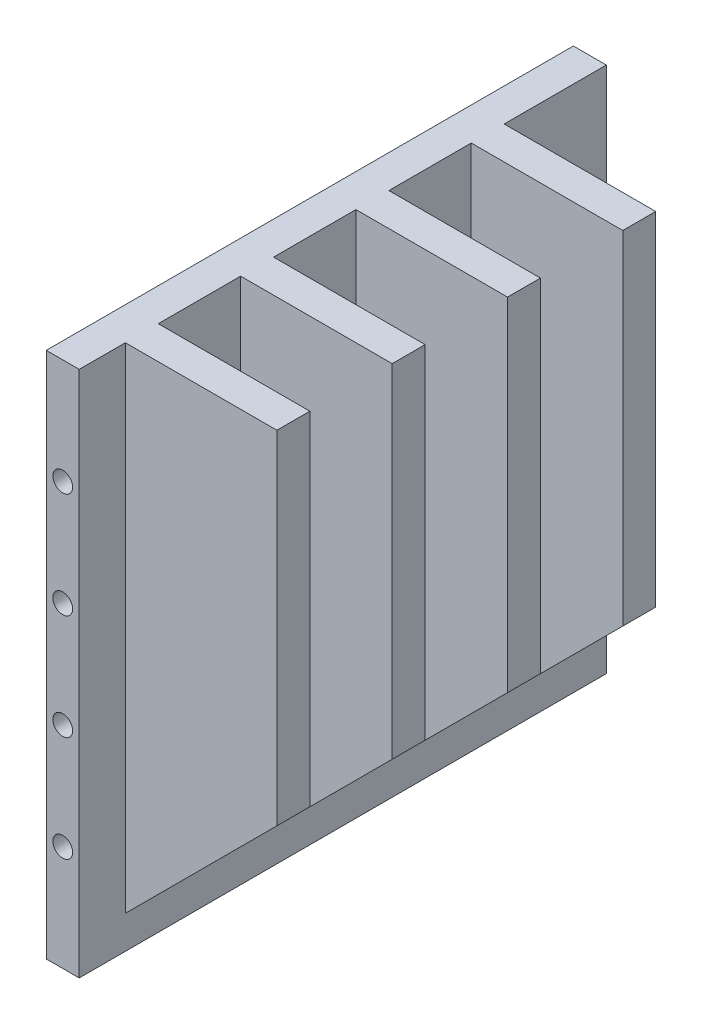
SolidWorks part; units mm, degrees
material "ABS"
ref_plane "Front Plane" through (0, 0, 0) normal (0, 0, 1) x (1, 0, 0)
ref_plane "Top Plane" through (0, 0, 0) normal (0, 1, 0) x (1, 0, 0)
ref_plane "Right Plane" through (0, 0, 0) normal (1, 0, 0) x (0, 0, -1)
sketch "Sketch1" plane through (0, 0, 0) normal (0, 1, 0) x (1, 0, 0)
  line L0 (0, -19.05) -> (0, 19.05)
  line L1 (0, 19.05) -> (0, 52.07)
  line L2 (0, 52.07) -> (6.35, 52.07)
  line L3 (6.35, 52.07) -> (6.35, 19.05)
  line L4 (6.35, 19.05) -> (6.35, -19.05)
  line L5 (6.35, -19.05) -> (6.35, -49.53)
  line L6 (6.35, -49.53) -> (0, -49.53)
  line L7 (0, -49.53) -> (0, -19.05)
  dimension "D1" = 6.35
  dimension "D2" = 101.6
  dimension "D3" = 38.1
  dimension "D4" = 30.48
  dimension "D5" = 6.35
  dimension "D6" = 0
extrude "Boss-Extrude1" add sketch "Sketch1" along normal blind 101.6
sketch "Sketch2" plane through (0, 0, 49.53) normal (0, 0, 1) x (1, 0, 0)
  line L0 (0, 0) -> (6.35, 0) construction
  line L2 (0, 101.6) -> (0, 0) construction
  circle A0 centre (3.175, 81.28) radius 1.905
  circle A1 centre (3.175, 60.96) radius 1.905
  circle A2 centre (3.175, 20.32) radius 1.905
  circle A3 centre (3.175, 40.64) radius 1.905
  dimension "D1" = 3.81
  dimension "D2" = 20.32
  dimension "D3" = 20.32
  dimension "D4" = 20.32
  dimension "D5" = 20.32
  dimension "D6" = 3.175
extrude "Cut-Extrude1" cut sketch "Sketch2" against normal blind 4.826
mirror "Mirror1" about plane through (0, 0, 0) normal (0, 0, 1) of "Cut-Extrude1"
sketch "Sketch5" plane through (0, 101.6, 0) normal (0, 1, 0) x (1, 0, 0)
  line L22 (0, 52.07) -> (0, -49.53) construction
  line L23 (6.35, 32.385) -> (35.56, 32.385)
  line L24 (6.35, 32.385) -> (6.35, 26.035)
  line L25 (6.35, 26.035) -> (35.56, 26.035)
  line L26 (35.56, 32.385) -> (35.56, 26.035)
  line L27 (6.35, 10.16) -> (35.56, 10.16)
  line L28 (6.35, 10.16) -> (6.35, 3.81)
  line L29 (6.35, 3.81) -> (35.56, 3.81)
  line L30 (35.56, 10.16) -> (35.56, 3.81)
  line L31 (6.35, -12.065) -> (35.56, -12.065)
  line L32 (6.35, -12.065) -> (6.35, -18.415)
  line L33 (6.35, -18.415) -> (35.56, -18.415)
  line L34 (35.56, -12.065) -> (35.56, -18.415)
  line L35 (6.35, -34.29) -> (35.56, -34.29)
  line L36 (6.35, -34.29) -> (6.35, -40.64)
  line L37 (6.35, -40.64) -> (35.56, -40.64)
  line L38 (35.56, -34.29) -> (35.56, -40.64)
  line L39 (0, -49.53) -> (6.35, -49.53) construction
  dimension "D2" = 6.35
  dimension "D3" = 6.35
  dimension "D8" = 15.875
  dimension "D9" = 15.875
  dimension "D10" = 15.875
  dimension "D11" = 8.89
  dimension "D12" = 35.56
extrude "Boss-Extrude2" add sketch "Sketch5" against normal blind 57.15
chamfer "Chamfer1" distance 38.1 angle 45 4 edges at (6.35, 44.45, -29.21) (6.35, 44.45, -6.985) (6.35, 44.45, 15.24) (6.35, 44.45, 37.465)
extrude "Cut-Extrude2" cut sketch "Sketch2<2>" along normal blind 4.826 from surface starting at face at (3.175, 50.8, -52.07)
sketch "Sketch2<2>" plane through (0, 0, 49.53) normal (0, 0, 1) x (1, 0, 0) same geometry as "Sketch2"
